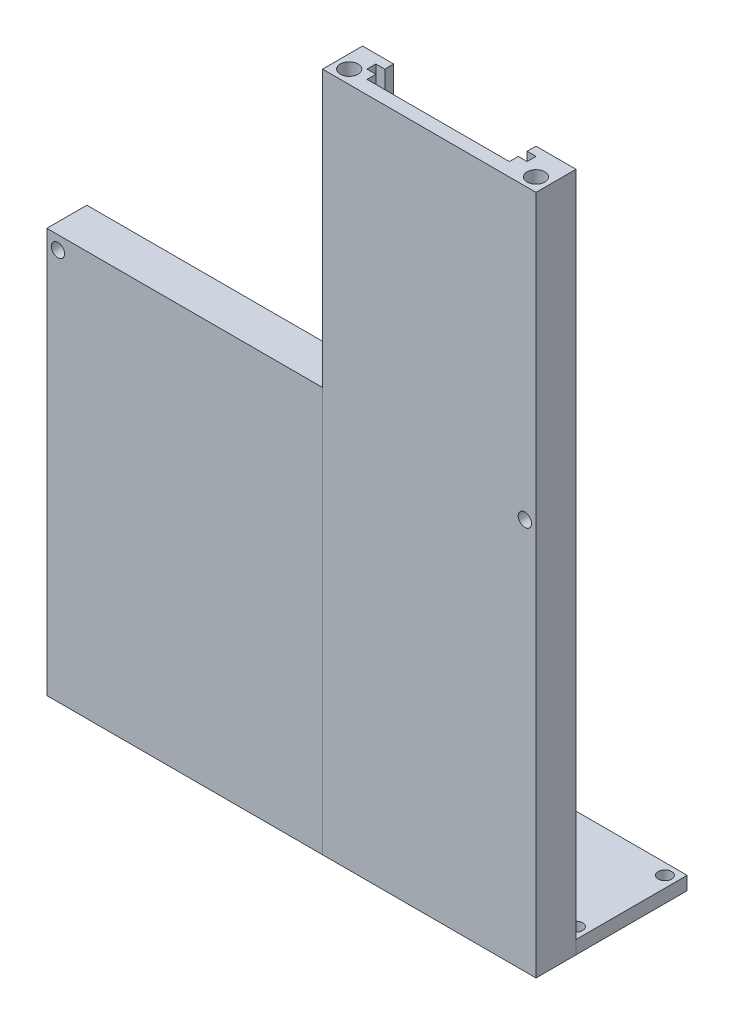
SolidWorks part; units mm, degrees
ref_plane "Přední rovina" through (0, 0, 0) normal (0, 0, 1) x (1, 0, 0)
ref_plane "Horní rovina" through (0, 0, 0) normal (0, 1, 0) x (1, 0, 0)
ref_plane "Pravá rovina" through (0, 0, 0) normal (1, 0, 0) x (0, 0, -1)
sketch "Skica1" plane through (0, 0, 0) normal (0, 0, 1) x (1, 0, 0)
  line L1 (45, -3) -> (40, -3)
  line L2 (45, -3) -> (45, 150)
  line L4 (40, 0) -> (40, 150)
  line L6 (-3, -3) -> (0, -3)
  line L7 (-3, -3) -> (-3, 150)
  line L9 (0, 0) -> (0, 150)
  line L10 (0, 150) -> (0, 115) construction
  line L11 (-3, 112) -> (-3, 153) construction
  line L12 (40, 115) -> (40, 150) construction
  line L13 (0, 150) -> (-3, 150)
  line L18 (0, -3) -> (40, -3)
  line L20 (0, 0) -> (40, 0)
  line L22 (40, 150) -> (45, 150)
  line L23 (40, 150) -> (45, 150) construction
  line L25 (40, 0) -> (40, -3) construction
  line L26 (0, 0) -> (0, -3) construction
  dimension "D1" = 3
  dimension "D2" = 5
extrude "Přidat vysunutím1" add sketch "Skica1" along normal blind 6 contours L4 L1 L2 | L4 L9 | L6 L9 L7 region at (42.5, -1.3965, 0)
sketch "Skica2" plane through (0, 0, 6) normal (0, 0, 1) x (1, 0, 0)
  line L11 (-3, -3) -> (45, -3)
  line L12 (-3, -3) -> (-3, 150)
  line L13 (-3, 150) -> (45, 150)
  line L14 (45, -3) -> (45, 150)
extrude "Přidat vysunutím2" add sketch "Skica2" along normal blind 3
sketch "Skica3" plane through (0, -3, 0) normal (0, -1, 0) x (1, 0, 0)
  line L1 (3, 3) -> (0, 3) construction
  line L2 (0, 0) -> (4, 0)
  line L3 (0, 0) -> (0, 6)
  line L4 (0, 6) -> (4, 6)
  line L5 (4, 0) -> (4, 2)
  line L6 (40, 0) -> (36, 0)
  line L7 (40, 0) -> (40, 6)
  line L8 (40, 6) -> (36, 6)
  line L9 (36, 0) -> (36, 2)
  line L10 (37, 3) -> (40, 3) construction
  line L11 (2, 2) -> (4, 2)
  line L12 (2, 2) -> (2, 4)
  line L13 (2, 4) -> (4, 4)
  line L15 (2, 2) -> (4, 4) construction
  line L16 (2, 4) -> (4, 2) construction
  line L17 (36, 4) -> (36, 6)
  line L18 (38, 2) -> (36, 2)
  line L19 (38, 2) -> (38, 4)
  line L20 (38, 4) -> (36, 4)
  line L22 (38, 2) -> (36, 4) construction
  line L23 (38, 4) -> (36, 2) construction
  line L24 (4, 4) -> (4, 6)
  line L25 (-3, 0) -> (45, 0) construction
  line L26 (45, 9) -> (45, 0) construction
  point P15 (3, 3)
  point P22 (37, 3)
  dimension "D1" = 4
  dimension "D2" = 4
  dimension "D3" = 2
  dimension "D4" = 2
  dimension "D5" = 2
  dimension "D6" = 2
  dimension "D7" = 2
  dimension "D8" = 2
  dimension "D9" = 2
  dimension "D10" = 2
  dimension "D11" = 32
  dimension "D12" = 36
sketch "Skica5" plane through (0, 0, 9) normal (0, 0, 1) x (1, 0, 0)
  line L0 (-65, 0) -> (-65, 88) construction
  line L1 (-3, 88) -> (-65, 88) construction
  line L2 (-65, -3) -> (-3, -3)
  line L3 (-65, -3) -> (-65, 88)
  line L4 (-65, 88) -> (-3, 88)
  line L5 (-3, -3) -> (-3, 88)
  line L8 (-3, -3) -> (45, -3) construction
  line L9 (-3, 150) -> (-3, -3) construction
  point P2 (-63, -3)
extrude "Přidat vysunutím4" add sketch "Skica5" against normal blind 7.5 separate body
ref_plane "Rovina1" through (-65, -3, 1.5) normal (1, 0, 0) x (0, 0, -1)
sketch "Skica7" plane through (0, 0, 1.5) normal (0, 0, -1) x (-1, 0, 0)
  line L0 (62, 0) -> (62, 85)
  line L1 (65, -3) -> (3, -3)
  line L2 (65, -3) -> (65, 88)
  line L3 (65, 88) -> (3, 88)
  line L4 (3, -3) -> (3, 88)
  line L5 (62, 85) -> (6, 85)
  line L6 (6, 0) -> (6, 85)
  line L7 (62, 0) -> (6, 0)
  dimension "D1" = 3
extrude "Přidat vysunutím5" add sketch "Skica7" along normal through all
extrude "Přidat vysunutím6" add sketch "Skica3" against normal through all
sketch "Skica9" plane through (0, 0, 0) normal (0, 0, -1) x (-1, 0, 0)
  line L0 (3, -3) -> (-45, -3) construction
  line L1 (-4, -3) -> (6, -3)
  line L2 (-4, -3) -> (-4, 57)
  line L3 (-4, 57) -> (6, 57)
  line L4 (6, -3) -> (6, 57)
  line L5 (6, 85) -> (6, 0) construction
  line L6 (-4, 150) -> (-4, 0) construction
  line L7 (62, 85) -> (6, 85) construction
  line L8 (6, 57) -> (-4, 57)
  line L9 (6, 57) -> (6, 85)
  line L10 (6, 85) -> (-4, 85)
  line L11 (-4, 57) -> (-4, 85)
  line M14 (3, -3) -> (3, 150)
  line M16 (-4, 150) -> (-4, 0)
  dimension "D1" = 60
extrude "Odebrat vysunutím2" cut sketch "Skica9" against normal blind 1.5 contours L10 L3 M14 M16 | L9 L10 L3 M14 region at (-4.5, 71, 0) region at (0.5, 71, 0)
sketch "Skica10" plane through (0, 0, 0) normal (0, 0, -1) x (-1, 0, 0)
  line L0 (65, -3) -> (65, 88) construction
  line L1 (-45, -3) -> (65, -3)
  line L2 (-45, -3) -> (-45, 0)
  line L3 (-45, 0) -> (65, 0)
  line L4 (65, -3) -> (65, 0)
  line L5 (6, 0) -> (62, 0) construction
extrude "Přidat vysunutím7" add sketch "Skica10" along normal blind 25 separate body
sketch "Skica11" plane through (0, 0, 0) normal (0, 1, 0) x (1, 0, 0)
  line L0 (-33, 5) -> (-39, 5) construction
  line L1 (-33, 3.5) -> (-39, 3.5)
  line L2 (-33, 6.5) -> (-39, 6.5)
  line L3 (-6, 0) -> (-62, 0) construction
  line L4 (-65, 0) -> (45, 0) construction
  circle A0 centre (-18, 5) radius 2.5
  arc A1 (-33, 3.5) -> (-33, 6.5) centre (-33, 5) ccw
  arc A2 (-39, 6.5) -> (-39, 3.5) centre (-39, 5) ccw
  point P4 (-36, 5)
  point P11 (-3, 0)
  dimension "D1" = 5
  dimension "D3" = 6
  dimension "D4" = 1.5
  dimension "D2" = 3
  dimension "D5" = 5
  dimension "D6" = 15
  dimension "D7" = 15
extrude "Odebrat vysunutím3" cut sketch "Skica11" against normal through all
sketch "Skica12" plane through (0, 0, 1.5) normal (0, 0, -1) x (-1, 0, 0)
  line L0 (62, 0) -> (62, 85) construction
  line L1 (51, 71) -> (51, 85) construction
  line L2 (62, 85) -> (3, 85) construction
  line L3 (6, 0) -> (62, 0) construction
  line L4 (-36, 150) -> (-36, 0) construction
  line L5 (62, 85) -> (3, 85) construction
  circle A0 centre (51, 71) radius 2
  circle A1 centre (29, 73) radius 2
  circle A2 centre (-26, 73) radius 2
  circle A3 centre (51, 16) radius 2
  dimension "D1" = 4
  dimension "D2" = 11
  dimension "D3" = 55
  dimension "D4" = 55
  dimension "D5" = 14
  dimension "D6" = 16
  dimension "D7" = 10
  dimension "D8" = 12
  dimension "D9" = 22
extrude "Vysunout tenkostěnný1" add sketch "Skica12" along normal up to surface (1.5 mm away) and the other way up to surface (4.5 mm away) separate body thin up to face at (-27.8, 45.4, 0) other way up to face at (20, 75, 6) thin type one direction wall 3
sketch "Skica13" plane through (0, 150, 0) normal (0, 1, 0) x (1, 0, 0)
  line L0 (45, -9) -> (-3, -9) construction
  line L1 (45, -9) -> (45, 0) construction
  line L2 (-3, -9) -> (-3, 0) construction
  circle A0 centre (42, -6) radius 2
  circle A1 centre (0, -6) radius 2
  dimension "D1" = 4
  dimension "D2" = 3
  dimension "D3" = 3
  dimension "D4" = 3
extrude "Odebrat vysunutím4" cut sketch "Skica13" against normal blind 5
sketch "Skica14" plane through (0, -3, 0) normal (0, -1, 0) x (1, 0, 0)
  circle A0 centre (-62.5, -2.5) radius 1.5
  circle A1 centre (-62.5, -22.5) radius 1.5
  circle A2 centre (42.5, -2.5) radius 1.5
  circle A3 centre (42.5, -22.5) radius 1.5
  circle A4 centre (-62.5, -2.5) radius 2 construction
  circle A10 centre (-62.5, -22.5) radius 2 construction
  circle A11 centre (42.5, -2.5) radius 2 construction
  circle A12 centre (42.5, -22.5) radius 2 construction
  dimension "D1" = 3
extrude "Odebrat vysunutím6" cut sketch "Skica14" against normal through all both and the other way through all
sketch "Skica15" plane through (0, 0, 9) normal (0, 0, 1) x (1, 0, 0)
  circle A0 centre (-62.5, 85) radius 1.5
  circle A1 centre (42.5, 85) radius 1.5
  circle A2 centre (-62.5, 85) radius 2 construction
  circle A3 centre (42.5, 85) radius 1.9104 construction
  dimension "D1" = 3
extrude "Odebrat vysunutím7" cut sketch "Skica15" against normal through all both and the other way through all
sketch "Skica16" plane through (0, 0, 1.5) normal (0, 0, -1) x (-1, 0, 0)
  arc A0 (62, 83.5858) -> (61, 85) centre (62.5, 85) cw
  arc A1 (61, 85) -> (62, 83.5858) centre (62.5, 85) ccw construction
  circle A2 centre (62.5, 85) radius 2.5
  arc M2 (62, 83.5858) -> (61, 85) centre (62.5, 85) cw
  line M3 (61, 85) -> (3, 85)
  line M8 (62, 0) -> (62, 83.5858)
  dimension "D1" = 1
extrude "Přidat vysunutím8" add sketch "Skica16" along normal up to surface (1.5 mm away) contours A2 M3 M8 M2 region at (-60.9991, 83.8302, 1.5) up to face at (-31.0204, 49.0144, 0)
